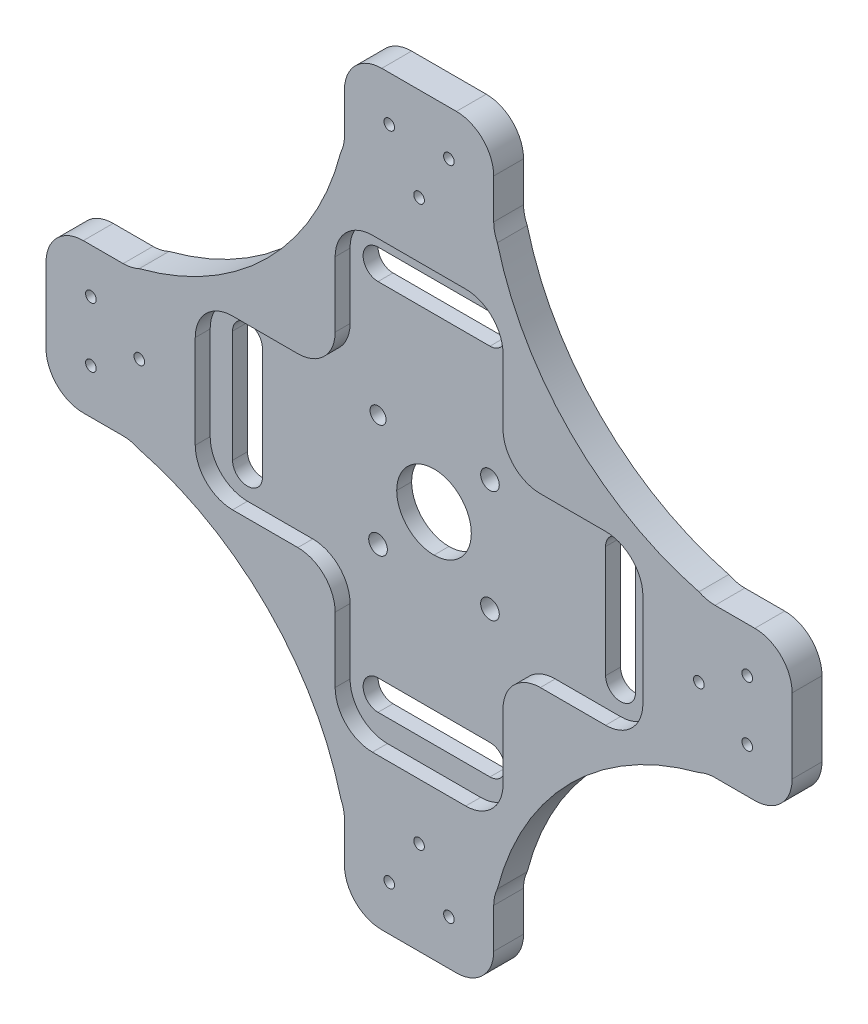
SolidWorks part; units mm, degrees
ref_plane "Front Plane" through (0, 0, 0) normal (0, 0, 1) x (1, 0, 0)
ref_plane "Top Plane" through (0, 0, 0) normal (0, 1, 0) x (1, 0, 0)
ref_plane "Right Plane" through (0, 0, 0) normal (1, 0, 0) x (0, 0, -1)
sketch "Sketch1" plane through (0, 0, 0) normal (0, 0, 1) x (1, 0, 0)
  line L13 (-100, -100) -> (100, -100)
  line L14 (-100, -100) -> (-100, 100)
  line L15 (-100, 100) -> (100, 100)
  line L16 (100, -100) -> (100, 100)
  line L17 (-100, -100) -> (100, 100) construction
  line L18 (-100, 100) -> (100, -100) construction
  line L19 (-75, -75) -> (75, -75)
  line L20 (-75, -75) -> (-75, 75)
  line L21 (-75, 75) -> (75, 75)
  line L22 (75, -75) -> (75, 75)
  line L23 (-75, -75) -> (75, 75) construction
  line L24 (-75, 75) -> (75, -75) construction
  line L39 (-75, -24.9122) -> (-75, 26.5574)
  line L48 (-100, -20.0021) -> (-75, -20.0021)
  line L49 (-75, -20.0021) -> (-75, 20.0021)
  line L50 (-75, 20.0021) -> (-100, 20.0021)
  line L51 (-100, 20.0021) -> (-100, -20.0021)
  line L64 (-72, -72) -> (-72, 72)
  line L65 (-72, 72) -> (72, 72)
  line L70 (72, -72) -> (72, 72)
  line L71 (-72, -72) -> (72, -72)
  line L72 (-10.5, -75) -> (10.5, -75)
  line L77 (75, -10.5) -> (64, -10.5)
  line L78 (75, -10.5) -> (75, 10.5)
  line L79 (75, 10.5) -> (64, 10.5)
  line L80 (64, -10.5) -> (64, 10.5)
  line L81 (-10.5, -75) -> (-10.5, -64)
  line L82 (-10.5, -64) -> (10.5, -64)
  line L83 (10.5, -75) -> (10.5, -64)
  line L84 (-75, 10.5) -> (-75, -10.5)
  line L85 (-75, 10.5) -> (-64, 10.5)
  line L86 (-64, 10.5) -> (-64, -10.5)
  line L87 (-75, -10.5) -> (-64, -10.5)
  line L88 (10.5, 75) -> (-10.5, 75)
  line L89 (10.5, 75) -> (10.5, 64)
  line L90 (10.5, 64) -> (-10.5, 64)
  line L91 (-10.5, 75) -> (-10.5, 64)
  line L92 (-75, 45) -> (-72, 45)
  line L93 (-45, 75) -> (-45, 72)
  line L94 (-20.0021, 100) -> (-20.0021, 75)
  line L95 (-20.0021, 75) -> (20.0021, 75)
  line L96 (20.0021, 75) -> (20.0021, 100)
  line L97 (20.0021, 100) -> (-20.0021, 100)
  line L98 (100, 20.0021) -> (75, 20.0021)
  line L99 (75, 20.0021) -> (75, -20.0021)
  line L100 (75, -20.0021) -> (100, -20.0021)
  line L101 (100, -20.0021) -> (100, 20.0021)
  line L102 (20.0021, -100) -> (20.0021, -75)
  line L103 (20.0021, -75) -> (-20.0021, -75)
  line L104 (-20.0021, -75) -> (-20.0021, -100)
  line L105 (-20.0021, -100) -> (20.0021, -100)
  line L106 (-87.5, 20.0021) -> (-87.5, -20.0021) construction
  circle A12 centre (-87.9698, 8) radius 1.425
  circle A13 centre (-87.9698, -8) radius 1.425
  circle A14 centre (-75, 0) radius 1.425
  circle A15 centre (8, 87.9698) radius 1.425
  circle A16 centre (0, 75) radius 1.425
  circle A17 centre (-8, 87.9698) radius 1.425
  circle A18 centre (87.9698, -8) radius 1.425
  circle A19 centre (75, 0) radius 1.425
  circle A20 centre (87.9698, 8) radius 1.425
  circle A21 centre (-8, -87.9698) radius 1.425
  circle A22 centre (0, -75) radius 1.425
  circle A23 centre (8, -87.9698) radius 1.425
  point P0 (0, 0)
  point P5 (-87.5, 0)
  point P6 (-64, 0)
  point P11 (0, 0)
  point P85 (0, 0)
  dimension "D3" = 2.85
  dimension "D1" = 200
  dimension "D2" = 200
  dimension "D4" = 150
  dimension "D5" = 4
  dimension "D8" = 11
  dimension "D7" = 21
  dimension "D10" = 45
  dimension "D11" = 45
  dimension "D9" = 4
extrude "Boss-Extrude1" add sketch "Sketch1" along normal mid plane 8 contours A14 L49 L39 L50 L14 L48 A13 A12 | A14 L49 L87 L64 L85 | L64 L87 L86 L85 | L91 L65 L64 L85 L86 L87 L71 L81 L82 L83 L70 L77 L80 L79 L89 L90 | L92 L20 L39 L85 L64 | A22 L19 L104 L13 L102 A23 A21 | A19 L22 L100 L16 L98 A20 A18 | A16 L21 L96 L15 L94 A17 A15 | L87 L39 L20 L19 L81 L71 L64 | L83 L19 L22 L77 L70 L71 | A22 L19 L83 L71 L81 | L21 L89 L65 L70 L79 L22 | L21 L93 L65 L91 | L93 L21 L20 L92 L64 L65 | L65 L91 L90 L89 | A16 L21 L91 L65 L89 | L80 L77 L70 L79 | A19 L22 L79 L70 L77 | L71 L83 L82 L81 region at (0, -87.5325, 0) region at (-87.5325, 0, 0) region at (-47.501, -74.0878, 0) region at (15.251, -74.0878, 0) region at (0, -73.4523, 0) region at (-73.5, 27.75, 0) region at (-73.4523, 0, 0) region at (87.5325, 0, 0) region at (0, -68, 0) region at (0, 0, 0) region at (0, 87.5325, 0) region at (-68, 0, 0) region at (-27.75, 73.5, 0) region at (-74.5757, 60, 0) region at (74.0878, 15.251, 0) region at (73.4523, 0, 0) region at (0, 73.4523, 0) region at (68, 0, 0) region at (0, 68, 0)
sketch "Sketch6" plane through (0, 0, 0) normal (0, 0, 1) x (1, 0, 0)
  line L7 (-15, 50) -> (15, 50) construction
  line L9 (-15, 54) -> (15, 54)
  line L16 (0, -4.4) -> (0, 4.4) construction
  line L18 (4.4, 0) -> (-4.4, 0) construction
  line L24 (-15, 46) -> (15, 46)
  line L25 (-20.9897, -100) -> (20.9897, -100)
  line L26 (-20.9897, -100) -> (-20.9897, 100)
  line L27 (-20.9897, 100) -> (20.9897, 100)
  line L28 (20.9897, -100) -> (20.9897, 100)
  line L29 (-20.9897, -100) -> (20.9897, 100) construction
  line L30 (-20.9897, 100) -> (20.9897, -100) construction
  line L31 (-100, -20.9897) -> (100, -20.9897)
  line L32 (-100, -20.9897) -> (-100, 20.9897)
  line L33 (-100, 20.9897) -> (100, 20.9897)
  line L34 (100, -20.9897) -> (100, 20.9897)
  line L35 (-100, -20.9897) -> (100, 20.9897) construction
  line L36 (-100, 20.9897) -> (100, -20.9897) construction
  line L37 (50, 15) -> (50, -15) construction
  line L38 (54, 15) -> (54, -15)
  line L39 (46, 15) -> (46, -15)
  line L40 (15, -50) -> (-15, -50) construction
  line L41 (15, -54) -> (-15, -54)
  line L42 (15, -46) -> (-15, -46)
  line L43 (-50, -15) -> (-50, 15) construction
  line L44 (-54, -15) -> (-54, 15)
  line L45 (-46, -15) -> (-46, 15)
  line L46 (-75, 20.9897) -> (-75, -20.9897) construction
  line L47 (-10, -10) -> (10, -10)
  line L48 (-10, -10) -> (-10, 10)
  line L49 (-10, 10) -> (10, 10)
  line L50 (10, -10) -> (10, 10)
  line L51 (-10, -10) -> (10, 10) construction
  line L52 (-10, 10) -> (10, -10) construction
  line L53 (-75, 75) -> (-20.0021, 75) construction
  line L54 (-20, -20) -> (20, -20)
  line L55 (-20, -20) -> (-20, 20)
  line L56 (-20, 20) -> (20, 20)
  line L57 (20, -20) -> (20, 20)
  line L58 (-20, -20) -> (20, 20) construction
  line L59 (-20, 20) -> (20, -20) construction
  arc A3 (-75, 20.9897) -> (-20.9897, 75) centre (-93.8629, 93.8629) ccw
  arc A4 (-15, 54) -> (-15, 46) centre (-15, 50) ccw
  arc A5 (15, 46) -> (15, 54) centre (15, 50) ccw
  arc A6 (54, 15) -> (46, 15) centre (50, 15) ccw
  arc A7 (46, -15) -> (54, -15) centre (50, -15) ccw
  arc A8 (15, -54) -> (15, -46) centre (15, -50) ccw
  arc A9 (-15, -46) -> (-15, -54) centre (-15, -50) ccw
  arc A10 (-54, -15) -> (-46, -15) centre (-50, -15) ccw
  arc A11 (-46, 15) -> (-54, 15) centre (-50, 15) ccw
  arc A12 (75, 20.9897) -> (20.9897, 75) centre (93.8629, 93.8629) cw
  arc A13 (75, -20.9897) -> (20.9897, -75) centre (93.8629, -93.8629) ccw
  arc A14 (-75, -20.9897) -> (-20.9897, -75) centre (-93.8629, -93.8629) cw
  point P0 (0, 0)
  point P5 (0, 0)
  point P14 (0, 50)
  point P30 (0, 0)
  point P36 (0, 0)
  point P40 (50, 0)
  point P47 (0, -50)
  point P54 (-50, 0)
  point P62 (0, 0)
  point P67 (-75, 0)
  point P68 (0, 0)
  point P69 (0, 0)
  point P70 (0, 0)
  dimension "D1" = 20
  dimension "D7" = 40
  dimension "D2" = 50
  dimension "D3" = 8
  dimension "D4" = 30
  dimension "D6" = 20
  dimension "D8" = 40
  dimension "D5" = 4
extrude "Cut-Extrude15" cut sketch "Sketch6" against normal mid plane 10 flip side to cut contours L31 L34 L33 L28 A7 L39 A6 L38 | L33 A12 L28 | A3 L33 L26 | L26 L33 L28 L27 A5 L24 A4 L9 | L31 A14 L26 | L31 L26 L25 L28 A9 L42 A8 L41 | A13 L31 L28 | L54 L57 L56 L55 L50 L47 L48 L49 | L33 L26 L31 L28 L57 L54 L55 L56 | L33 L32 L31 L26 A11 L45 A10 L44 region at (0, -61.5014, 0) region at (-35.4657, -35.4657, 0) region at (35.4657, -35.4657, 0) region at (-61.5014, 0, 0) region at (-20.396, 0, 0) region at (61.5014, 0, 0) region at (-35.4657, 35.4657, 0) region at (0, 61.5014, 0) region at (35.4657, 35.4657, 0) region at (-19.4343, 0, 0)
sketch "Sketch8" plane through (0, 0, 0) normal (0, 0, 1) x (1, 0, 0)
  line L1 (-60, -22.5) -> (60, -22.5)
  line L2 (-60, -22.5) -> (-60, 22.5)
  line L3 (-60, 22.5) -> (60, 22.5)
  line L4 (60, -22.5) -> (60, 22.5)
  line L5 (-60, -22.5) -> (60, 22.5) construction
  line L6 (-60, 22.5) -> (60, -22.5) construction
  line L7 (-22.5, -60) -> (22.5, -60)
  line L8 (-22.5, -60) -> (-22.5, 60)
  line L9 (-22.5, 60) -> (22.5, 60)
  line L10 (22.5, -60) -> (22.5, 60)
  line L11 (-22.5, -60) -> (22.5, 60) construction
  line L12 (-22.5, 60) -> (22.5, -60) construction
  line L13 (-19, -19) -> (19, -19) construction
  line L14 (-19, -19) -> (-19, 19) construction
  line L15 (-19, 19) -> (19, 19) construction
  line L16 (19, -19) -> (19, 19) construction
  line L17 (-19, -19) -> (19, 19) construction
  line L18 (-19, 19) -> (19, -19) construction
  point P0 (0, 0)
  point P6 (0, 0)
  point P11 (0, 0)
  dimension "D1" = 45
  dimension "D2" = 120
  dimension "D3" = 45
  dimension "D4" = 120
  dimension "D9" = 38
  dimension "D10" = 38
extrude "Cut-Extrude16" cut sketch "Sketch8" against normal blind 4 from surface contours L9 L10 L7 L8 | L3 L4 L1 L2 starting at face at (0, 50, 4)
sketch "Sketch10" plane through (0, 0, 0) normal (0, 0, 1) x (1, 0, 0)
  line L1 (-15, -15) -> (15, -15) construction
  line L2 (-15, -15) -> (-15, 15) construction
  line L3 (-15, 15) -> (15, 15) construction
  line L4 (15, -15) -> (15, 15) construction
  line L5 (-15, -15) -> (15, 15) construction
  line L6 (-15, 15) -> (15, -15) construction
  circle A0 centre (-15, 15) radius 2.15
  circle A1 centre (15, 15) radius 2.5
  circle A2 centre (15, -15) radius 3.5
  circle A3 centre (15, 15) radius 3.5
  circle A4 centre (-15, 15) radius 3.5
  circle A5 centre (-15, -15) radius 3.5
  circle A6 centre (-15, -15) radius 2.5
  circle A7 centre (15, -15) radius 2.5
  point P0 (0, 0)
  dimension "D1" = 7
  dimension "D2" = 4.3
  dimension "D3" = 7
  dimension "D4" = 5
  dimension "D5" = 5
  dimension "D6" = 7
  dimension "D7" = 5
  dimension "D8" = 7
  dimension "D9" = 30
  dimension "D10" = 30
extrude "Cut-Extrude17" cut sketch "Sketch10" along normal blind 6 from surface contours A1 | A0 | A6 | A7 region at (-15, 15, 0) region at (15, 15, 0) region at (-15, -15, 0) region at (15, -15, 0) starting at face at (0, 0, -4)
fillet "Fillet1" radius 10 16 edges at (-22.5, -60, 2) (22.5, -60, 2) (60, -22.5, 2) (60, 22.5, 2) (22.5, 60, 2) (-22.5, 60, 2) (-60, 22.5, 2) (-60, -22.5, 2) (10, -10, -2) (-10, -10, -2) (10, 10, -2) (-10, 10, -2) (22.5, -22.5, 2) (-22.5, -22.5, 2) (22.5, 22.5, 2) (-22.5, 22.5, 2)
fillet "Fillet3" radius 10 8 edges at (-100, 20.0021, 0) (-100, -20.0021, 0) (-20.0021, -100, 0) (20.0021, -100, 0) (100, -20.0021, 0) (100, 20.0021, 0) (20.0021, 100, 0) (-20.0021, 100, 0)
fillet "Fillet4" radius 10 8 edges at (75, 20.0021, 0) (75, -20.0021, 0) (20.0021, -75, 0) (-20.0021, -75, 0) (-75, -20.0021, 0) (-75, 20.0021, 0) (20.0021, 75, 0) (-20.0021, 75, 0)
